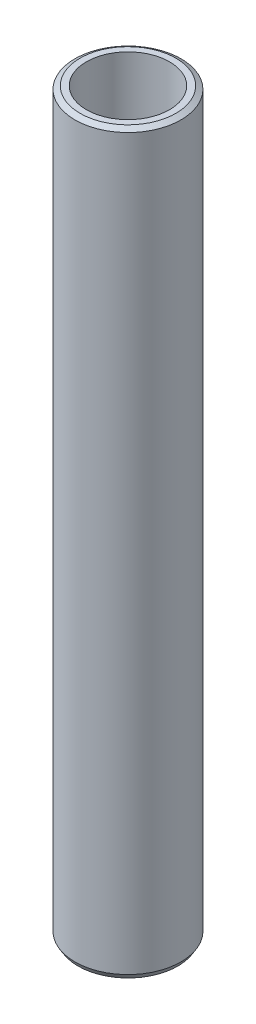
SolidWorks part; units mm, degrees
ref_plane "Front Plane" through (0, 0, 0) normal (0, 0, 1) x (1, 0, 0)
ref_plane "Top Plane" through (0, 0, 0) normal (0, 1, 0) x (1, 0, 0)
ref_plane "Right Plane" through (0, 0, 0) normal (1, 0, 0) x (0, 0, -1)
sketch "Sketch1" plane through (0, 0, 0) normal (0, 1, 0) x (1, 0, 0)
  circle A0 centre (0, 0) radius 37.5
  dimension "SHAFT_OD" = 75
extrude "Boss-Extrude1" add sketch "Sketch1" along normal blind 521.5383
sketch "Sketch2" plane through (0, 0, 0) normal (0, 1, 0) x (1, 0, 0)
  circle A0 centre (0, 0) radius 29.3927
  dimension "BORE_D" = 58.7854
extrude "Cut-Extrude1" cut sketch "Sketch2" along normal through all
chamfer "Chamfer1" distance 2.1698 angle 59.146 2 edges at (0, 521.5383, 37.5) (0, 0, 37.5) first distance on face at (0, 521.5383, 37.5) first distance on face at (0, 0, 29.3927)
